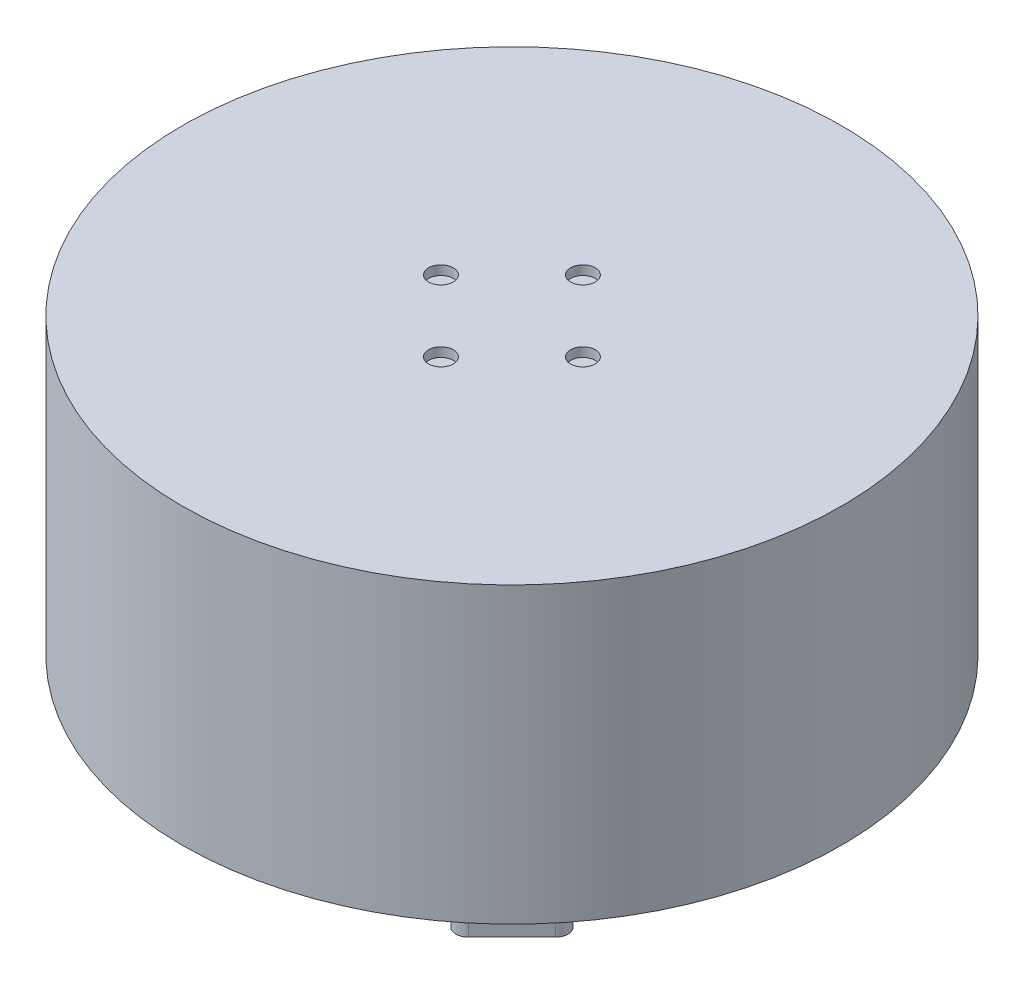
SolidWorks part; units mm, degrees
ref_plane "Front Plane" through (0, 0, 0) normal (0, 0, 1) x (1, 0, 0)
ref_plane "Top Plane" through (0, 0, 0) normal (0, 1, 0) x (1, 0, 0)
ref_plane "Right Plane" through (0, 0, 0) normal (1, 0, 0) x (0, 0, -1)
sketch "Sketch1" plane through (0, 0, 0) normal (0, 1, 0) x (1, 0, 0)
  circle A0 centre (0, 0) radius 53.4
  dimension "D1" = 106.8
extrude "Boss-Extrude1" add sketch "Sketch1" along normal blind 47.6
sketch "Sketch2" plane through (0, 0, 0) normal (0, -1, 0) x (1, 0, 0)
  circle A0 centre (0, 0) radius 20 construction
  circle A1 centre (0, 20) radius 2.5
  circle A2 centre (20, 0) radius 2.5
  circle A3 centre (0, -20) radius 2.5
  circle A4 centre (-20, 0) radius 2.5
  point P14 (0, 0)
  dimension "D1" = 40
  dimension "D2" = 5
  dimension "D3" = 4
extrude "Cut-Extrude1" cut sketch "Sketch2" against normal blind 1.5
sketch "Sketch3" plane through (0, 0, 0) normal (0, -1, 0) x (1, 0, 0)
  line L0 (0, 0) -> (0, 20) construction
  line L1 (0, 20) -> (20, 0) construction
  line L2 (20, 0) -> (0, 0) construction
  line L3 (0, 0) -> (32.1734, 32.1734) construction
  line L4 (28.6378, 35.7089) -> (35.7089, 28.6378) construction
  line L5 (30.7591, 37.8302) -> (37.8302, 30.7591) construction
  line L6 (26.5165, 33.5876) -> (33.5876, 26.5165) construction
  line L7 (30.052, 37.1231) -> (37.1231, 30.052)
  line L8 (27.2236, 34.2947) -> (34.2947, 27.2236)
  arc A0 (30.7591, 37.8302) -> (26.5165, 33.5876) centre (28.6378, 35.7089) ccw construction
  arc A1 (33.5876, 26.5165) -> (37.8302, 30.7591) centre (35.7089, 28.6378) ccw construction
  arc A2 (34.2947, 27.2236) -> (37.1231, 30.052) centre (35.7089, 28.6378) ccw
  arc A3 (30.052, 37.1231) -> (27.2236, 34.2947) centre (28.6378, 35.7089) ccw
  point P9 (32.1734, 32.1734)
  dimension "D3" = 3
  dimension "D1" = 45.5
  dimension "D2" = 10
  dimension "D4" = 1
extrude "Boss-Extrude2" add sketch "Sketch3" along normal blind 6
sketch "Sketch4" plane through (0, 47.6, 0) normal (0, 1, 0) x (1, 0, 0)
  circle A0 centre (0, 0) radius 11.5 construction
  circle A1 centre (0, 11.5) radius 2
  circle A2 centre (11.5, 0) radius 2
  circle A3 centre (0, -11.5) radius 2
  circle A4 centre (-11.5, 0) radius 2
  point P14 (0, 0)
  dimension "D3" = 4
  dimension "D1" = 23
  dimension "D2" = 4
extrude "Cut-Extrude2" cut sketch "Sketch4" against normal blind 1.5
equation "\"Np_b\" = 48"
equation "\"module\" = 0.6"
equation "\"pressure angle\" = 20.0"
equation "\"h_a\" = 0.6"
equation "\"h_b\" = 0.75"
equation "\"clr_tip_root\" = 0.15000000000000002"
equation "\"fw_p_s\" = 30.231545005724083"
equation "\"Nr_s\" = 128"
equation "\"pressure_angle\" = 20.0"
equation "\"h_f\" = 0.75"
equation "\"dp_r_s\" = 76.8"
equation "\"db_r_s\" = 72.16839327635776"
equation "\"fw_r_s\" = 28.731545005724083"
equation "\"alpha_r_s\" = 0.8539582918412556"
equation "\"beta_r_s\" = 3.114166583682511"
equation "\"bearing_ID\" = 65"
equation "\"bearing_OD\" = 85"
equation "\"bearing_height\" = 10"
equation "\"clearance_planet\" = 1.5"
equation "\"case_dist\" = 6.5"
equation "\"Motor_case_OD_max\" = 131.3"
equation "\"case_mounting_PCD\" = 123.8"
equation "\"bearing mount thickness\" = 8"
equation "\"case_mounting_hole_dia\" = 3"
equation "\"output_mounting_PCD\" = 93"
equation "\"output_mounting_hole_dia\" = 4"
equation "\"clearance_case_mount_holes_shell_thickness\" = 1"
equation "\"motor_case_OD_base\" = 121.8"
equation "\"sec_carrier_thickness\" = 5"
equation "\"sun_coupler_hub_thickness\" = 4"
equation "\"clearance_sun_coupler_sec_carrier\" = 1.5"
equation "\"clearance_motor_and_case\" = 5"
equation "\"motor_OD\" = 106.8"
equation "\"Motor_case_thickness\" = 2.5"
equation "\"Motor_case_ID\" = 116.8"
equation "\"case_mounting_hole_shift\" = 1.0"
equation "\"output_mounting_nut_wrench_size\" = 7"
equation "\"output_mounting_nut_thickness\" = 3.2"
equation "\"case_mounting_hole_allen_socket_dia\" = 5.5"
equation "\"output_mounting_nut_depth\" = 3"
equation "\"case_mounting_bolt_depth\" = 4.5"
equation "\"Ns\" = 48"
equation "\"ring_radial_thickness\" = 5"
equation "\"ring_OD\"= \"Nr_s\" * \"module\" + \"ring_radial_thickness\" * 2"
equation "\"ring_to_chamfer_clearance\" = 1.5"
equation "\"Motor_case_OD_base_to_chamfer\" = 5"
equation "\"pattern_offset_from_motor_case_OD_base\" = 3"
equation "\"pattern_bulge_dia\" = 3"
equation "\"pattern_num_bulge\" = 18"
equation "\"pattern_depth\" = 2"
equation "\"motor_height\" = 47.6"
equation "\"case_mounting_wrench_size\" = 5.5"
equation "\"case_mounting_nut_clearance\" = 2"
equation "\"base_plate_thickness\" = 4"
equation "\"case_mounting_nut_thickness\" = 2.4"
equation "\"case_mounting_surface_height\" = 4"
equation "\"motor_mount_hole_PCD\" = 40"
equation "\"motor_mount_hole_dia\" = 5"
equation "\"motor_mount_hole_num\" = 4"
equation "\"central_hole_offset_from_motor_mount_PCD\" = 5"
equation "\"wire_slot_dist_from_center\" = 45.5"
equation "\"wire_slot_length\" = 10"
equation "\"wire_slot_radius\" = 3"
equation "\"driver_upper_holes_dist_from_center\" = 29"
equation "\"driver_lower_holes_dist_from_center\" = 13"
equation "\"driver_side_holes_dist_from_center\" = 22.5"
equation "\"driver_mount_holes_dia\" = 3"
equation "\"driver_mount_inserts_OD\" = 4.8"
equation "\"driver_mount_thickness\" = 1.5"
equation "\"driver_mount_height\" = 6"
equation "\"air_flow_hole_offset\" = 3"
equation "\"num_planet\" = 4"
equation "\"planet_pin_bolt_dia\" = 5"
equation "\"planet_pin_socket_head_dia\" = 8.5"
equation "\"carrier_PCD\" = 57.599999999999994"
equation "\"planet_shaft_dia\" = 8"
equation "\"planet_shaft_step_offset\" = 1"
equation "\"carrier_trapezoidal_support_sun_offset\" = 5"
equation "\"carrier_trapezoidal_support_hole_PCD_offset_bearing_ID\" = 4"
equation "\"carrier_trapezoidal_support_hole_dia\" = 3"
equation "\"carrier_trapezoidal_support_hole_socket_head_dia\" = 5.5"
equation "\"carrier_bearing_step_width\" = 1.5"
equation "\"standard_clearance_1_5mm\" = 1.5"
equation "\"standard_fillet_1_5mm\" = 1.5"
equation "\"sun_shaft_bearing_OD\" = 16"
equation "\"sun_shaft_bearing_width\" = 5"
equation "\"standard_bearing_insertion_chamfer\" = 0.5"
equation "\"carrier_trapezoidal_support_hole_wrench_size\" = 5.5"
equation "\"planet_pin_bolt_wrench_size\" = 8"
equation "\"planet_bearing_OD\" = 12"
equation "\"planet_bearing_width\" = 3.5"
equation "\"planet_bore\" = 10"
equation "\"D1@Boss-Extrude1\"=\"motor_height\""
equation "\"D1@Sketch1\"=\"motor_OD\""
equation "\"D1@Sketch2\"=\"motor_mount_hole_PCD\""
equation "\"D2@Sketch2\"=\"motor_mount_hole_dia\""
equation "\"D3@Sketch2\"=\"motor_mount_hole_num\""
equation "\"D1@Cut-Extrude1\"=\"standard_clearance_1_5mm\""
equation "\"D1@Sketch3\"=\"wire_slot_dist_from_center\""
equation "\"D2@Sketch3\"=\"wire_slot_length\""
equation "\"D3@Sketch3\"=\"wire_slot_radius\""
equation "\"D1@Boss-Extrude2\"=\"standard_clearance_1_5mm\"*4"
equation "\"motor_output_hole_PCD\" = 23"
equation "\"motor_output_hole_dia\" = 4"
equation "\"motor_output_hole_num\" = 4"
equation "\"D1@Sketch4\"=\"motor_output_hole_PCD\""
equation "\"D2@Sketch4\"=\"motor_output_hole_dia\""
equation "\"D3@Sketch4\"=\"motor_output_hole_num\""
equation "\"D1@Cut-Extrude2\"=\"standard_clearance_1_5mm\""
equation "\"dp_s\" = 28.799999999999997"
equation "\"db_s\" = 27.06314747863416"
equation "\"fw_s_calc\" = 7.664359769718526"
equation "\"alpha_s\" = 0.8539582918412343"
equation "\"beta_s\" = 2.0420834163175314"
equation "\"dp_p_b\" = 28.799999999999997"
equation "\"db_p_b\" = 27.06314747863416"
equation "\"alpha_p_b\" = 0.8539582918412343"
equation "\"beta_p_b\" = 2.0420834163175314"
equation "\"sun_shaft_bearing_ID\" = 8"
equation "\"sun_hub_dia\" = 30.0"
equation "\"sun_central_bolt_dia\" = 5"
equation "\"sun_central_bolt_socket_head_dia\" = 8.5"
equation "\"fw_s_used\" = 72.54334182621932"
equation "\"motor_output_hole_CSK_OD\" = 8"
equation "\"motor_output_hole_CSK_head_height\" = 2.0"
equation "\"bearing_retainer_thickness\" = 2"
equation "\"Np_s\" = 32"
equation "\"fw_p_b\" = 34.81179682049524"
equation "\"dp_p_s\" = 19.2"
equation "\"db_p_s\" = 18.04209831908944"
equation "\"alpha_p_s\" = 0.8539582918412556"
equation "\"beta_p_s\" = 3.917083416317489"
equation "\"clr_tip_root_s\" = 0.15000000000000002"
equation "\"Nr_b\" = 144"
equation "\"fw_r_b\" = 34.81179682049524"
equation "\"dp_r_b\" = 86.39999999999999"
equation "\"db_r_b\" = 81.18944243590248"
equation "\"alpha_r_b\" = 0.8539582918412414"
equation "\"beta_r_b\" = 2.957916583682483"
equation "\"ring_OD_b\" = 96.39999999999999"
equation "\"small_ring_case_thickness\" = 4"
equation "\"carrier_thickness\" = 4"
equation "\"small_ring_output_wall_thickness\" = 5"
equation "\"small_ring_output_wall_to_bearing_shaft_attachement_hole_dia\" = 4"
equation "\"small_ring_output_wall_to_bearing_shaft_attachement_hole_depth\" = 6.5"
equation "\"small_ring_output_wall_to_bearing_shaft_attachement_nut_wrench\" = 7"
equation "\"small_ring_output_wall_to_bearing_shaft_attachement_nut_thickness\" = 3.2"
equation "\"small_ring_output_wall_to_bearing_shaft_attachement_hole_pcd\" = 12"
equation "\"small_ring_output_wall_to_bearing_shaft_attachement_hole_num\" = 3"
equation "\"small_ring_output_wall_to_bearing_shaft_attachement_hole_CSK_OD\" = 8"
equation "\"small_ring_output_wall_to_bearing_shaft_attachement_hole_CSK_head_height\" = 2.0"
equation "\"carrier_small_ring_inner_bearing_ID\" = 20"
equation "\"carrier_small_ring_inner_bearing_OD\" = 32"
equation "\"carrier_small_ring_inner_bearing_height\" = 7"
equation "\"carrier_small_ring_inner_bearing_flap\" = 2"
equation "\"gear_casing_big_ring_to_bearing_dist\" = 39.23154500572409"
equation "\"gear_casing_thickness\" = 4"
